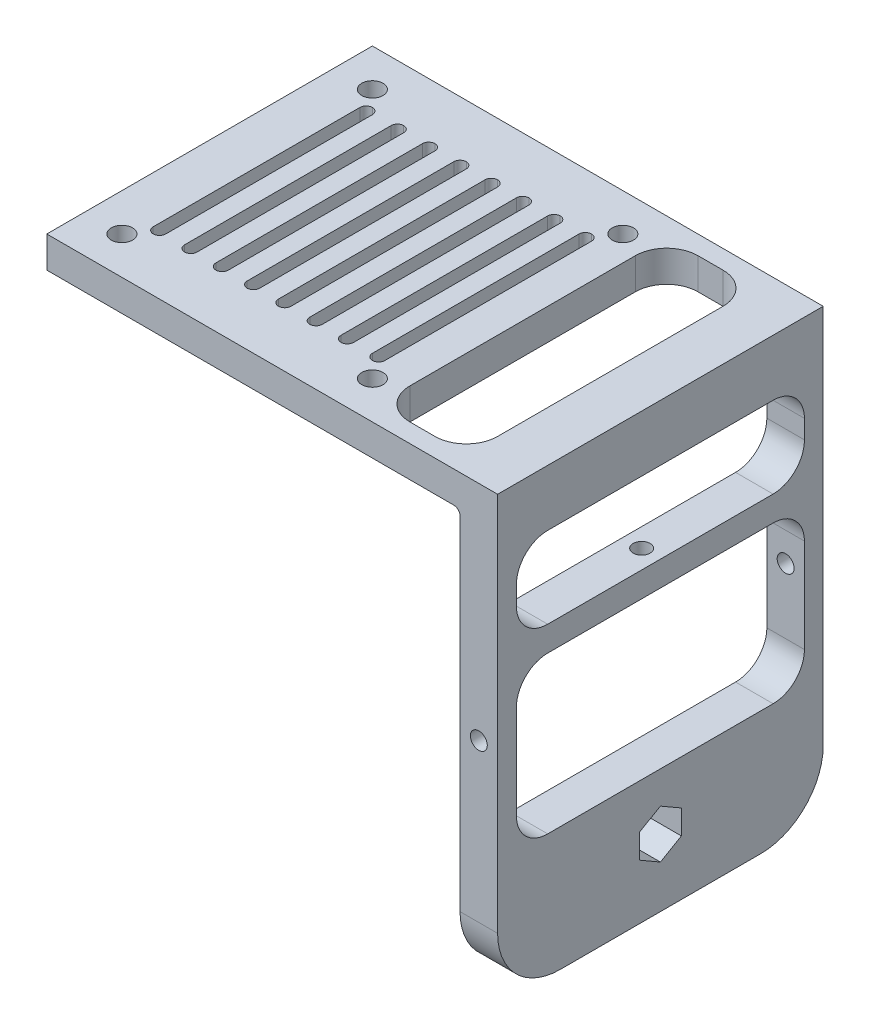
SolidWorks part; units mm, degrees
ref_plane "Front Plane" through (0, 0, 0) normal (0, 0, 1) x (1, 0, 0)
ref_plane "Top Plane" through (0, 0, 0) normal (0, 1, 0) x (1, 0, 0)
ref_plane "Right Plane" through (0, 0, 0) normal (1, 0, 0) x (0, 0, -1)
sketch "Sketch1" plane through (0, 0, 0) normal (0, 1, 0) x (1, 0, 0)
  line L0 (6, 46) -> (6, 6) construction
  line L1 (0, 0) -> (66, 0)
  line L2 (0, 0) -> (0, 52)
  line L3 (0, 52) -> (66, 52)
  line L4 (66, 0) -> (66, 52)
  line L5 (6, 6) -> (46, 6) construction
  line L6 (46, 6) -> (46, 46) construction
  line L7 (46, 46) -> (6, 46) construction
  circle A0 centre (6, 46) radius 1.7
  circle A1 centre (46, 46) radius 1.7
  circle A2 centre (46, 6) radius 1.7
  circle A3 centre (6, 6) radius 1.7
  dimension "D5" = 3.4
  dimension "D6" = 3.4
  dimension "D7" = 3.4
  dimension "D8" = 3.4
  dimension "D1" = 6
  dimension "D2" = 20
  dimension "D3" = 6
  dimension "D4" = 6
  dimension "D9" = 40
  dimension "D10" = 40
extrude "Boss-Extrude1" add sketch "Sketch1" along normal blind 5
sketch "Sketch2" plane through (0, 5, 0) normal (0, 1, 0) x (1, 0, 0)
  line L0 (0, 0) -> (66, 0) construction
  line L1 (66, 52) -> (72, 52)
  line L2 (66, 52) -> (66, 0)
  line L3 (66, 0) -> (72, 0)
  line L4 (72, 52) -> (72, 0)
  dimension "D1" = 6
  dimension "D2" = 0
extrude "Boss-Extrude2" add sketch "Sketch2" against normal blind 100
sketch "Sketch5" plane through (0, 5, 0) normal (0, 1, 0) x (1, 0, 0)
  line L0 (0, 26) -> (72, 26) construction
  line L1 (7.5, 8.5) -> (9.5, 8.5)
  line L2 (7.5, 8.5) -> (7.5, 43.5)
  line L3 (7.5, 43.5) -> (9.5, 43.5)
  line L4 (9.5, 8.5) -> (9.5, 43.5)
  line L5 (0, 52) -> (0, 0) construction
  line L6 (72, 0) -> (72, 52) construction
  dimension "D1" = 17.5
  dimension "D2" = 35
  dimension "D3" = 7.5
  dimension "D4" = 2
extrude "Cut-Extrude4" cut sketch "Sketch5" against normal blind 10 contours L2 L3 L4 L1
fillet "Fillet1" radius 1 4 edges at (7.5, 2.5, -43.5) (9.5, 2.5, -43.5) (9.5, 2.5, -8.5) (7.5, 2.5, -8.5)
pattern_linear "LPattern1" count 8 spacing 5 along (1, 0, 0) of "Fillet1", "Cut-Extrude4"
sketch "Sketch6" plane through (66, 0, 0) normal (-1, 0, 0) x (0, 0, 1)
  line L0 (-52, -95) -> (-52, 0) construction
  line L1 (2.3191, -65.7279) -> (-52, -65.7279)
  line L2 (2.3191, -65.7279) -> (2.3191, -97.9677)
  line L3 (2.3191, -97.9677) -> (-52, -97.9677)
  line L4 (-52, -65.7279) -> (-52, -97.9677)
  line L5 (2.3191, -65.7279) -> (-52, -97.9677) construction
  line L6 (2.3191, -97.9677) -> (-52, -65.7279) construction
  point P0 (-24.8405, -81.8478)
extrude "Cut-Extrude5" cut sketch "Sketch6" against normal blind 10
sketch "Sketch7" plane through (0, 0, 0) normal (0, -1, 0) x (1, 0, 0)
  line L0 (55, -49) -> (59, -49)
  line L1 (64, -44) -> (64, -8)
  line L2 (59, -3) -> (55, -3)
  line L3 (50, -8) -> (50, -44)
  line L4 (66, -52) -> (0, -52) construction
  line L5 (0, 0) -> (66, 0) construction
  line L6 (66, 0) -> (66, -52) construction
  circle A0 centre (46, -46) radius 1.7 construction
  arc A1 (55, -3) -> (50, -8) centre (55, -8) ccw
  arc A2 (64, -8) -> (59, -3) centre (59, -8) ccw
  arc A3 (59, -49) -> (64, -44) centre (59, -44) ccw
  arc A4 (55, -49) -> (50, -44) centre (55, -44) cw
  dimension "D5" = 5
  dimension "D1" = 3
  dimension "D2" = 3
  dimension "D3" = 2
  dimension "D4" = 4
extrude "Cut-Extrude6" cut sketch "Sketch7" against normal blind 10
fillet "Fillet2" radius 10 2 edges at (69, -65.7279, 0) (69, -65.7279, -52)
sketch "Sketch9" plane through (66, 0, 0) normal (-1, 0, 0) x (0, 0, 1)
  line L0 (-26, 0) -> (-26, -65.7279) construction
  line L1 (0, 0) -> (-52, 0) construction
  line L2 (-10, -65.7279) -> (-42, -65.7279) construction
  line L4 (-26, -58.8682) -> (-22.65, -56.9341)
  line L5 (-22.65, -56.9341) -> (-22.65, -53.0659)
  line L6 (-22.65, -53.0659) -> (-26, -51.1318)
  line L7 (-26, -51.1318) -> (-29.35, -53.0659)
  line L8 (-29.35, -53.0659) -> (-29.35, -56.9341)
  line L9 (-29.35, -56.9341) -> (-26, -58.8682)
  circle A0 centre (-26, -55) radius 3.35 construction
  dimension "D1" = 6.7
  dimension "D2" = 55
extrude "Cut-Extrude7" cut sketch "Sketch9" against normal blind 10
sketch "Sketch10" plane through (66, 0, 0) normal (-1, 0, 0) x (0, 0, 1)
  line L0 (-44, -20.9721) -> (-8, -20.9721)
  line L1 (-3, -25.9721) -> (-3, -40.9721)
  line L2 (-8, -45.9721) -> (-44, -45.9721)
  line L3 (-49, -40.9721) -> (-49, -25.9721)
  line L4 (0, -55.7279) -> (0, 0) construction
  line L5 (-52, -55.7279) -> (-52, 0) construction
  arc A0 (-3, -40.9721) -> (-8, -45.9721) centre (-8, -40.9721) cw
  arc A1 (-44, -45.9721) -> (-49, -40.9721) centre (-44, -40.9721) cw
  arc A2 (-44, -20.9721) -> (-49, -25.9721) centre (-44, -25.9721) ccw
  arc A3 (-8, -20.9721) -> (-3, -25.9721) centre (-8, -25.9721) cw
  dimension "D3" = 5
  dimension "D4" = 15
  dimension "D1" = 3
  dimension "D2" = 3
extrude "Cut-Extrude8" cut sketch "Sketch10" against normal blind 10 contours L0 | L1 | L2 | L3 region at (66, -33.4721, -26)
fillet "Fillet3" radius 1 1 edges at (66, 0, -26)
sketch "Sketch11" plane through (0, 0, -52) normal (0, 0, -1) x (-1, 0, 0)
  line L2 (-72, 5) -> (0, 5) construction
  line L3 (-69, 5) -> (-69, -30.57) construction
  circle A0 centre (-69, -30.57) radius 1.35
  dimension "D1" = 2.7
extrude "Cut-Extrude9" cut sketch "Sketch11" against normal up to vertex (52 mm away) up to point (66, -1, 0)
sketch "Sketch13" plane through (0, -20.9721, 0) normal (0, -1, 0) x (1, 0, 0)
  line L0 (66, -26) -> (72, -26) construction
  line L1 (66, -44) -> (66, -8) construction
  line L2 (72, -8) -> (72, -44) construction
  circle A0 centre (69, -26) radius 1.35
  dimension "D1" = 2.7
extrude "Cut-Extrude11" cut sketch "Sketch13" against normal blind 10
sketch "Sketch15" plane through (66, 0, 0) normal (-1, 0, 0) x (0, 0, 1)
  line L4 (-3, -11.9721) -> (-3, -9)
  line L5 (-8, -4) -> (-44, -4)
  line L6 (-49, -9) -> (-49, -11.9721)
  line L7 (-44, -16.9721) -> (-8, -16.9721)
  line L8 (0, -55.7279) -> (0, -1) construction
  line L9 (-52, -55.7279) -> (-52, -1) construction
  line L10 (0, -1) -> (-52, -1) construction
  line L11 (-44, -20.9721) -> (-8, -20.9721) construction
  arc A2 (-49, -11.9721) -> (-44, -16.9721) centre (-44, -11.9721) ccw
  arc A3 (-44, -4) -> (-49, -9) centre (-44, -9) ccw
  arc A4 (-3, -9) -> (-8, -4) centre (-8, -9) ccw
  arc A5 (-3, -11.9721) -> (-8, -16.9721) centre (-8, -11.9721) cw
  point P11 (-26, -1)
  dimension "D5" = 5
  dimension "D1" = 3
  dimension "D2" = 3
  dimension "D3" = 3
  dimension "D4" = 4
extrude "Cut-Extrude12" cut sketch "Sketch15" against normal blind 10
